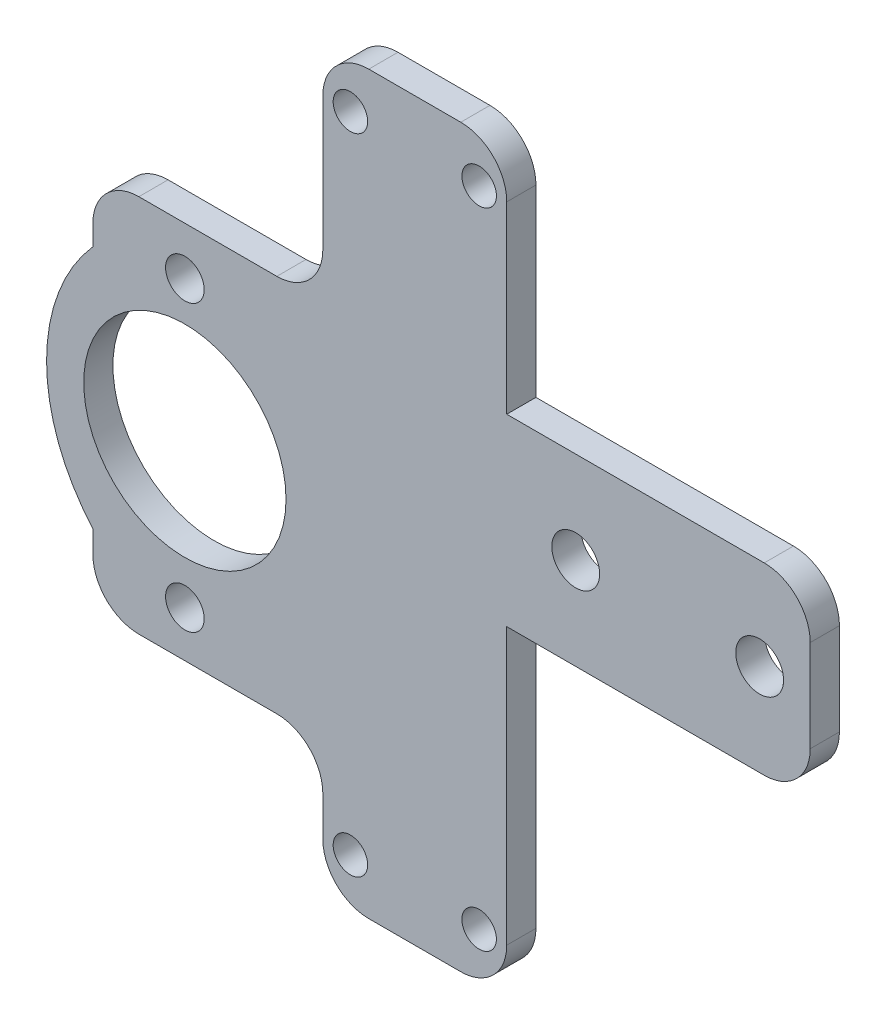
SolidWorks part; units mm, degrees
ref_plane "Front Plane" through (0, 0, 0) normal (0, 0, 1) x (1, 0, 0)
ref_plane "Top Plane" through (0, 0, 0) normal (0, 1, 0) x (1, 0, 0)
ref_plane "Right Plane" through (0, 0, 0) normal (1, 0, 0) x (0, 0, -1)
ref_plane "Plane1" through (0, 0, 0) normal (0, 0, -1) x (-1, 0, 0)
sketch "Sketch11" plane through (0, 0, 0) normal (0, 0, -1) x (-1, 0, 0)
  line L0 (20, 55.487) -> (5, 55.487)
  line L1 (0, 60.487) -> (0, 75)
  line L2 (-5, 80) -> (-15, 80)
  line L3 (-20, 75) -> (-20, 55)
  line L4 (-20, 55) -> (-48, 55)
  line L5 (-53, 50) -> (-53, 40)
  line L6 (-48, 35) -> (-20, 35)
  line L7 (-20, 35) -> (-20, 5)
  line L8 (-15, 0) -> (-5, 0)
  line L9 (0, 5) -> (0, 9.287)
  line L10 (5, 14.287) -> (20, 14.287)
  line L11 (25, 19.287) -> (25, 21.7285)
  line L12 (25, 48.2715) -> (25, 50.487)
  arc A0 (5, 55.487) -> (0, 60.487) centre (5, 60.487) cw
  arc A1 (0, 75) -> (-5, 80) centre (-5, 75) ccw
  arc A2 (-15, 80) -> (-20, 75) centre (-15, 75) ccw
  arc A3 (-48, 55) -> (-53, 50) centre (-48, 50) ccw
  arc A4 (-53, 40) -> (-48, 35) centre (-48, 40) ccw
  arc A5 (-20, 5) -> (-15, 0) centre (-15, 5) ccw
  arc A6 (-5, 0) -> (0, 5) centre (-5, 5) ccw
  arc A7 (0, 9.287) -> (5, 14.287) centre (5, 9.287) cw
  arc A8 (20, 14.287) -> (25, 19.287) centre (20, 19.287) ccw
  arc A9 (25, 21.7285) -> (25, 48.2715) centre (10.0378, 35) ccw
  arc A10 (25, 50.487) -> (20, 55.487) centre (20, 50.487) ccw
base flange "Base-Flange1" sketch "Sketch11" thickness 3.175 reverse thickness direction yes parameters "D1"=0
hole_wizard "M3.5 Clearance Hole1" positions "Sketch17" profile "Sketch16" hole size "M3.5" standard "ANSI Metric"
sketch "Sketch17" plane through (0, 0, 3.175) normal (0, 0, 1) x (1, 0, 0)
  point P0 (17, 5)
  point P1 (3, 75)
  point P2 (3, 5)
  point P3 (17, 75)
sketch "Sketch16" plane through (17, 5, 3.175) normal (1, 0, 0) x (0, -1, 0)
  line L0 (0, 0) -> (0, 3.175)
  line L1 (0, 3.175) -> (1.875, 3.175)
  line L2 (1.875, 3.175) -> (1.875, 0)
  line L5 (1.875, 0) -> (0, 0)
  line L11 (0, -6.35) -> (0, 107.95) construction
  dimension "Thru Hole Dia." = 3.75
  dimension "Thru Hole Depth" = 3.175
hole_wizard "Ø5.2 (5.2) Diameter Hole1" positions "Sketch19" profile "Sketch18" hole size "Ø5.2" standard "ANSI Metric"
sketch "Sketch19" plane through (0, 0, 3.175) normal (0, 0, 1) x (1, 0, 0)
  point P0 (27.5, 45)
  point P1 (47.5, 45)
sketch "Sketch18" plane through (27.5, 45, 3.175) normal (1, 0, 0) x (0, -1, 0)
  line L0 (0, 0) -> (0, 3.175)
  line L1 (0, 3.175) -> (2.6, 3.175)
  line L2 (2.6, 3.175) -> (2.6, 0)
  line L5 (2.6, 0) -> (0, 0)
  line L11 (0, -6.35) -> (0, 107.95) construction
  dimension "Thru Hole Dia." = 5.2
  dimension "Thru Hole Depth" = 3.175
hole_wizard "Ø4.2 (4.2) Diameter Hole1" positions "Sketch21" profile "Sketch20" hole size "Ø4.2" standard "ANSI Metric"
sketch "Sketch21" plane through (0, 0, 3.175) normal (0, 0, 1) x (1, 0, 0)
  point P0 (-15, 19.287)
  point P1 (-15, 50.275)
sketch "Sketch20" plane through (-15, 19.287, 3.175) normal (1, 0, 0) x (0, -1, 0)
  line L0 (0, 0) -> (0, 3.175)
  line L1 (0, 3.175) -> (2.1, 3.175)
  line L2 (2.1, 3.175) -> (2.1, 0)
  line L5 (2.1, 0) -> (0, 0)
  line L11 (0, -6.35) -> (0, 107.95) construction
  dimension "Thru Hole Dia." = 4.2
  dimension "Thru Hole Depth" = 3.175
hole_wizard "Ø22.0 (22) Diameter Hole1" positions "Sketch23" profile "Sketch22" hole size "Ø22.0" standard "ANSI Metric"
sketch "Sketch23" plane through (0, 0, 3.175) normal (0, 0, 1) x (1, 0, 0)
  point P0 (-15, 35)
sketch "Sketch22" plane through (-15, 35, 3.175) normal (1, 0, 0) x (0, -1, 0)
  line L0 (0, 0) -> (0, 3.175)
  line L1 (0, 3.175) -> (11, 3.175)
  line L2 (11, 3.175) -> (11, 0)
  line L5 (11, 0) -> (0, 0)
  line L11 (0, -6.35) -> (0, 107.95) construction
  dimension "Thru Hole Dia." = 22
  dimension "Thru Hole Depth" = 3.175
sketch "Bend-Lines4" plane through (0, 0, 0) normal (0, 1, 0) x (1, 0, 0)
sketch "Bounding-Box4" plane through (0, 0, 0) normal (0, 1, 0) x (1, 0, 0)
sheet metal parameters "Sheet-Metal(5)" thickness 3.175 parameters "D1"=0
flat pattern "Flat-Pattern(5)" [suppressed]
sketch "Bend-Lines5" plane through (0, 0, 0) normal (0, 1, 0) x (1, 0, 0)
sketch "Bounding-Box5" [suppressed] plane through (0, 0, 0) normal (0, 1, 0) x (1, 0, 0)
sheet metal parameters "Sheet-Metal(6)" thickness 3.175 parameters "D1"=0
flat pattern "Flat-Pattern(5)"
sketch "Bend-Lines5" plane through (0, 0, 0) normal (0, 1, 0) x (1, 0, 0)
sketch "Bounding-Box5" [suppressed] plane through (0, 0, 0) normal (0, 1, 0) x (1, 0, 0)
sheet metal parameters "Sheet-Metal(7)" thickness 3.175 parameters "D1"=0
flat pattern "Flat-Pattern(5)"
sketch "Bend-Lines5" plane through (0, 0, 0) normal (0, 1, 0) x (1, 0, 0)
sketch "Bounding-Box5" [suppressed] plane through (0, 0, 0) normal (0, 1, 0) x (1, 0, 0)
sheet metal parameters "Sheet-Metal(8)" thickness 3.175 parameters "D1"=0
flat pattern "Flat-Pattern(5)"
sketch "Bend-Lines5" plane through (0, 0, 0) normal (0, 1, 0) x (1, 0, 0)
sketch "Bounding-Box5" [suppressed] plane through (0, 0, 0) normal (0, 1, 0) x (1, 0, 0)
sheet metal parameters "Sheet-Metal(9)" thickness 3.175 parameters "D1"=0
flat pattern "Flat-Pattern(5)"
sketch "Bend-Lines5" plane through (0, 0, 0) normal (0, 1, 0) x (1, 0, 0)
sketch "Bounding-Box5" [suppressed] plane through (0, 0, 0) normal (0, 1, 0) x (1, 0, 0)
